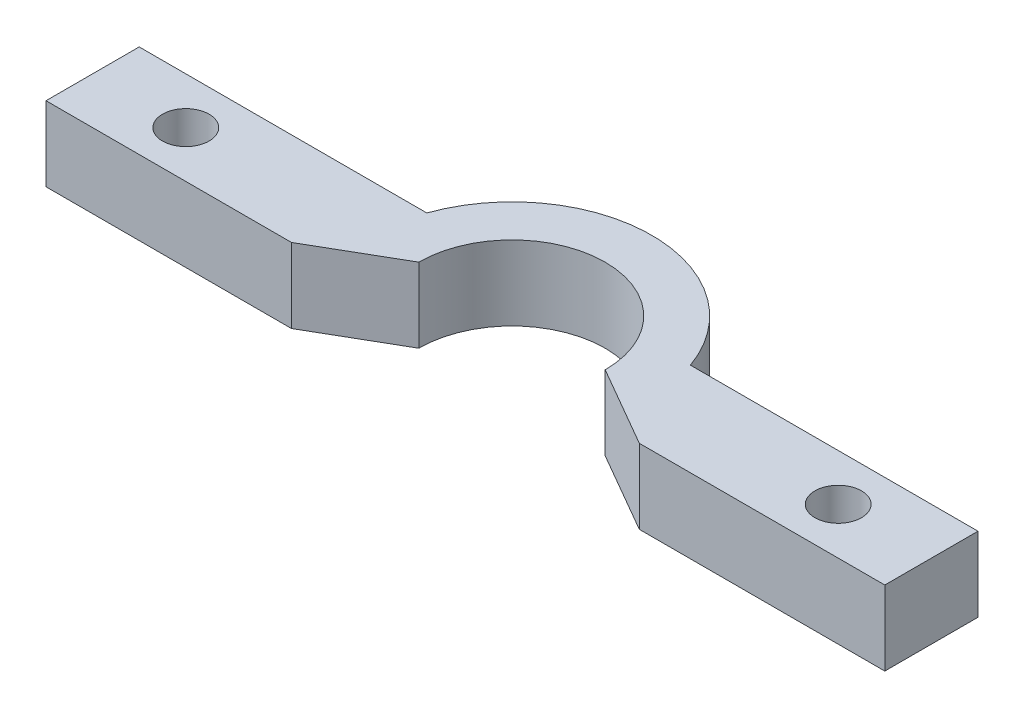
SolidWorks part; units mm, degrees
ref_plane "Front Plane" through (0, 0, 0) normal (0, 0, 1) x (1, 0, 0)
ref_plane "Top Plane" through (0, 0, 0) normal (0, 1, 0) x (1, 0, 0)
ref_plane "Right Plane" through (0, 0, 0) normal (1, 0, 0) x (0, 0, -1)
sketch "Sketch1" plane through (0, 0, 0) normal (0, 1, 0) x (1, 0, 0)
  line L0 (0, 0) -> (4.7625, 0)
  line L1 (-14.2875, -1.5875) -> (14.2875, -1.5875)
  line L2 (-14.2875, -1.5875) -> (-14.2875, 1.5875)
  line L3 (-14.2875, 1.5875) -> (14.2875, 1.5875)
  line L4 (14.2875, -1.5875) -> (14.2875, 1.5875)
  line L5 (-14.2875, -1.5875) -> (14.2875, 1.5875) construction
  line L6 (-14.2875, 1.5875) -> (14.2875, -1.5875) construction
  line L7 (4.7625, 0) -> (-4.7625, 0)
  line L8 (-3.175, 0) -> (-5.9246, -1.5875)
  line L9 (-5.9246, -1.5875) -> (5.9246, -1.5875)
  line L10 (5.9246, -1.5875) -> (3.175, 0)
  circle A0 centre (0, 0) radius 4.7625
  circle A1 centre (0, 0) radius 3.175
  circle A2 centre (-11.1125, 0) radius 0.7937
  circle A3 centre (11.1125, 0) radius 0.7937
  point P0 (0, 0)
  dimension "D3" = 1.5875
  dimension "D4" = 9.525
  dimension "D6" = 1.5875
  dimension "D7" = 3.175
  dimension "D1" = 28.575
  dimension "D2" = 3.175
  dimension "D5" = 3.175
  dimension "D8" = 3.175
extrude "Boss-Extrude1" add sketch "Sketch1" along normal mid plane 2.54 contours A0 L3 L2 L1 A2 | A1 L3 A0 L7 | A1 L3 A0 | A1 L7 A0 L3 | A0 L1 L4 L3 A3 | L7 A0 L8 | L10 A0 L7 region at (3.8522, 0, -0.8057) region at (4.2153, 0, 0.2925) region at (-4.2153, 0, 0.2925) region at (-3.8522, 0, -0.8057) region at (9.4449, 0, -0.0244) region at (0, 0, -3.1843) region at (-9.4449, 0, -0.0244)
